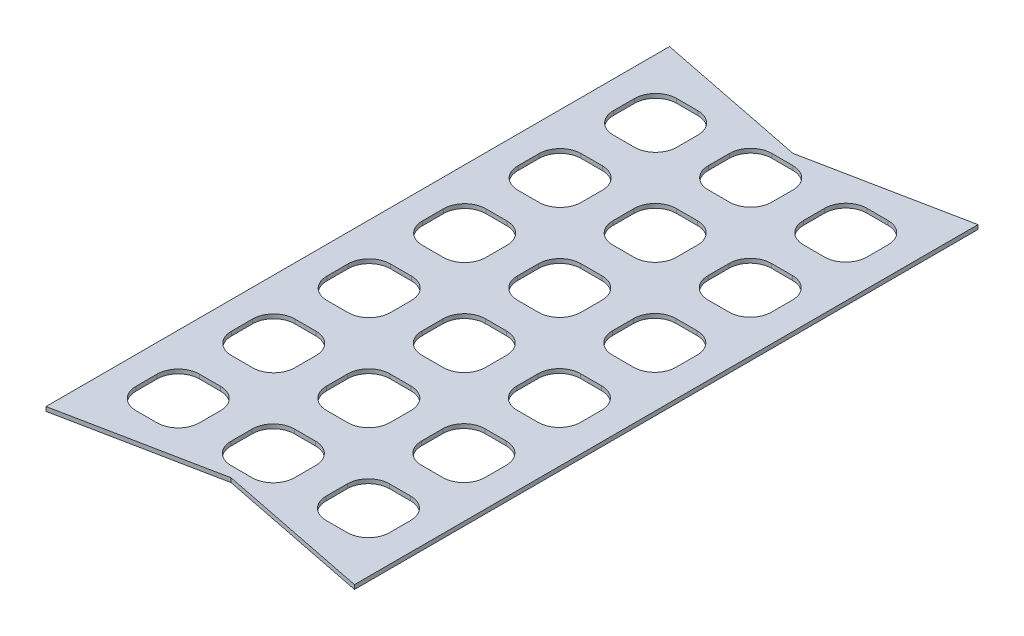
SolidWorks part; units mm, degrees
ref_plane "Front Plane" through (0, 0, 0) normal (0, 0, 1) x (1, 0, 0)
ref_plane "Top Plane" through (0, 0, 0) normal (0, 1, 0) x (1, 0, 0)
ref_plane "Right Plane" through (0, 0, 0) normal (1, 0, 0) x (0, 0, -1)
ref_axis "X" through (-88.99, 0, 0) along (1, 0, 0)
ref_axis "Y" through (0, 55, 0) along (0, -1, 0)
ref_axis "Z" through (0, 0, -88.99) along (0, 0, 1)
sketch "Sketch1" plane through (0, 0, 0) normal (0, 1, 0) x (1, 0, 0)
  line L0 (-75, 150) -> (0, 135) construction
  line L1 (-75, 150) -> (75, 150) construction
  line L2 (-75, 150) -> (-75, -150) construction
  line L3 (-75, -150) -> (75, -150) construction
  line L4 (75, 150) -> (75, -150) construction
  line L5 (-75, 150) -> (75, -150) construction
  line L6 (-75, -150) -> (75, 150) construction
  line L7 (0, 135) -> (75, 150) construction
  line L8 (-75, 0) -> (75, 0) construction
  line L9 (-75, -150) -> (0, -135) construction
  line L10 (0, -135) -> (75, -150) construction
  line L11 (-73, 147.5604) -> (-73, -147.5604)
  line L12 (-73, -147.5604) -> (0, -132.9604)
  line L13 (0, -132.9604) -> (73, -147.5604)
  line L14 (73, 147.5604) -> (73, -147.5604)
  line L15 (0, 132.9604) -> (73, 147.5604)
  line L16 (-73, 147.5604) -> (0, 132.9604)
  point P0 (0, 0)
  point P10 (-75, 150)
  dimension "D1" = 300
  dimension "D2" = 150
  dimension "D3" = 15
  dimension "D4" = 2
extrude "Boss-Extrude1" add sketch "Sketch1" along normal blind 2
sketch "Sketch2" plane through (0, 2, 0) normal (0, 1, 0) x (1, 0, 0)
  line L0 (-73, 147.5604) -> (-73, -147.5604) construction
  line L1 (-50, -127.9604) -> (-40, -127.9604)
  line L2 (-60, -117.9604) -> (-60, -107.9604)
  line L3 (-50, -97.9604) -> (-40, -97.9604)
  line L4 (-30, -117.9604) -> (-30, -107.9604)
  line L5 (-15, -117.9604) -> (-15, -107.9604)
  line L6 (-5, -127.9604) -> (5, -127.9604)
  line L7 (15, -117.9604) -> (15, -107.9604)
  line L8 (-5, -97.9604) -> (5, -97.9604)
  line L9 (30, -117.9604) -> (30, -107.9604)
  line L10 (40, -127.9604) -> (50, -127.9604)
  line L11 (60, -117.9604) -> (60, -107.9604)
  line L12 (40, -97.9604) -> (50, -97.9604)
  line L73 (-60, -72.7762) -> (-60, -62.7762)
  line L74 (-50, -82.7762) -> (-40, -82.7762)
  line L75 (-30, -72.7762) -> (-30, -62.7762)
  line L76 (-50, -52.7762) -> (-40, -52.7762)
  line L77 (-15, -72.7762) -> (-15, -62.7762)
  line L78 (-5, -52.7762) -> (5, -52.7762)
  line L79 (15, -72.7762) -> (15, -62.7762)
  line L80 (-5, -82.7762) -> (5, -82.7762)
  line L81 (30, -72.7762) -> (30, -62.7762)
  line L82 (40, -52.7762) -> (50, -52.7762)
  line L83 (60, -72.7762) -> (60, -62.7762)
  line L84 (40, -82.7762) -> (50, -82.7762)
  line L85 (-60, -27.5921) -> (-60, -17.5921)
  line L86 (-50, -37.5921) -> (-40, -37.5921)
  line L87 (-30, -27.5921) -> (-30, -17.5921)
  line L88 (-50, -7.5921) -> (-40, -7.5921)
  line L89 (-15, -27.5921) -> (-15, -17.5921)
  line L90 (-5, -7.5921) -> (5, -7.5921)
  line L91 (15, -27.5921) -> (15, -17.5921)
  line L92 (-5, -37.5921) -> (5, -37.5921)
  line L93 (30, -27.5921) -> (30, -17.5921)
  line L94 (40, -7.5921) -> (50, -7.5921)
  line L95 (60, -27.5921) -> (60, -17.5921)
  line L96 (40, -37.5921) -> (50, -37.5921)
  line L97 (-60, 17.5921) -> (-60, 27.5921)
  line L98 (-50, 7.5921) -> (-40, 7.5921)
  line L99 (-30, 17.5921) -> (-30, 27.5921)
  line L100 (-50, 37.5921) -> (-40, 37.5921)
  line L101 (-15, 17.5921) -> (-15, 27.5921)
  line L102 (-5, 37.5921) -> (5, 37.5921)
  line L103 (15, 17.5921) -> (15, 27.5921)
  line L104 (-5, 7.5921) -> (5, 7.5921)
  line L105 (30, 17.5921) -> (30, 27.5921)
  line L106 (40, 37.5921) -> (50, 37.5921)
  line L107 (60, 17.5921) -> (60, 27.5921)
  line L108 (40, 7.5921) -> (50, 7.5921)
  line L109 (-60, 62.7762) -> (-60, 72.7762)
  line L110 (-50, 52.7762) -> (-40, 52.7762)
  line L111 (-30, 62.7762) -> (-30, 72.7762)
  line L112 (-50, 82.7762) -> (-40, 82.7762)
  line L113 (-15, 62.7762) -> (-15, 72.7762)
  line L114 (-5, 82.7762) -> (5, 82.7762)
  line L115 (15, 62.7762) -> (15, 72.7762)
  line L116 (-5, 52.7762) -> (5, 52.7762)
  line L117 (30, 62.7762) -> (30, 72.7762)
  line L118 (40, 82.7762) -> (50, 82.7762)
  line L119 (60, 62.7762) -> (60, 72.7762)
  line L120 (40, 52.7762) -> (50, 52.7762)
  line L121 (-60, 107.9604) -> (-60, 117.9604)
  line L122 (-50, 97.9604) -> (-40, 97.9604)
  line L123 (-30, 107.9604) -> (-30, 117.9604)
  line L124 (-50, 127.9604) -> (-40, 127.9604)
  line L125 (-15, 107.9604) -> (-15, 117.9604)
  line L126 (-5, 127.9604) -> (5, 127.9604)
  line L127 (15, 107.9604) -> (15, 117.9604)
  line L128 (-5, 97.9604) -> (5, 97.9604)
  line L129 (30, 107.9604) -> (30, 117.9604)
  line L130 (40, 127.9604) -> (50, 127.9604)
  line L131 (60, 107.9604) -> (60, 117.9604)
  line L132 (40, 97.9604) -> (50, 97.9604)
  arc A0 (-60, -117.9604) -> (-50, -127.9604) centre (-50, -117.9604) ccw
  arc A1 (-40, -127.9604) -> (-30, -117.9604) centre (-40, -117.9604) ccw
  arc A2 (-30, -107.9604) -> (-40, -97.9604) centre (-40, -107.9604) ccw
  arc A3 (-50, -97.9604) -> (-60, -107.9604) centre (-50, -107.9604) ccw
  arc A4 (60, -107.9604) -> (50, -97.9604) centre (50, -107.9604) ccw
  arc A5 (50, -127.9604) -> (60, -117.9604) centre (50, -117.9604) ccw
  arc A6 (40, -127.9604) -> (30, -117.9604) centre (40, -117.9604) cw
  arc A7 (30, -107.9604) -> (40, -97.9604) centre (40, -107.9604) cw
  arc A8 (-15, -107.9604) -> (-5, -97.9604) centre (-5, -107.9604) cw
  arc A9 (-15, -117.9604) -> (-5, -127.9604) centre (-5, -117.9604) ccw
  arc A10 (15, -117.9604) -> (5, -127.9604) centre (5, -117.9604) cw
  arc A11 (15, -107.9604) -> (5, -97.9604) centre (5, -107.9604) ccw
  arc A12 (-50, -52.7762) -> (-60, -62.7762) centre (-50, -62.7762) ccw
  arc A13 (-60, -72.7762) -> (-50, -82.7762) centre (-50, -72.7762) ccw
  arc A14 (-40, -82.7762) -> (-30, -72.7762) centre (-40, -72.7762) ccw
  arc A15 (-30, -62.7762) -> (-40, -52.7762) centre (-40, -62.7762) ccw
  arc A16 (-15, -72.7762) -> (-5, -82.7762) centre (-5, -72.7762) ccw
  arc A17 (-15, -62.7762) -> (-5, -52.7762) centre (-5, -62.7762) cw
  arc A18 (15, -62.7762) -> (5, -52.7762) centre (5, -62.7762) ccw
  arc A19 (15, -72.7762) -> (5, -82.7762) centre (5, -72.7762) cw
  arc A20 (30, -62.7762) -> (40, -52.7762) centre (40, -62.7762) cw
  arc A21 (40, -82.7762) -> (30, -72.7762) centre (40, -72.7762) cw
  arc A22 (60, -62.7762) -> (50, -52.7762) centre (50, -62.7762) ccw
  arc A23 (50, -82.7762) -> (60, -72.7762) centre (50, -72.7762) ccw
  arc A24 (-50, -7.5921) -> (-60, -17.5921) centre (-50, -17.5921) ccw
  arc A25 (-60, -27.5921) -> (-50, -37.5921) centre (-50, -27.5921) ccw
  arc A26 (-40, -37.5921) -> (-30, -27.5921) centre (-40, -27.5921) ccw
  arc A27 (-30, -17.5921) -> (-40, -7.5921) centre (-40, -17.5921) ccw
  arc A28 (-15, -27.5921) -> (-5, -37.5921) centre (-5, -27.5921) ccw
  arc A29 (-15, -17.5921) -> (-5, -7.5921) centre (-5, -17.5921) cw
  arc A30 (15, -17.5921) -> (5, -7.5921) centre (5, -17.5921) ccw
  arc A31 (15, -27.5921) -> (5, -37.5921) centre (5, -27.5921) cw
  arc A32 (30, -17.5921) -> (40, -7.5921) centre (40, -17.5921) cw
  arc A33 (40, -37.5921) -> (30, -27.5921) centre (40, -27.5921) cw
  arc A34 (60, -17.5921) -> (50, -7.5921) centre (50, -17.5921) ccw
  arc A35 (50, -37.5921) -> (60, -27.5921) centre (50, -27.5921) ccw
  arc A36 (-50, 37.5921) -> (-60, 27.5921) centre (-50, 27.5921) ccw
  arc A37 (-60, 17.5921) -> (-50, 7.5921) centre (-50, 17.5921) ccw
  arc A38 (-40, 7.5921) -> (-30, 17.5921) centre (-40, 17.5921) ccw
  arc A39 (-30, 27.5921) -> (-40, 37.5921) centre (-40, 27.5921) ccw
  arc A40 (-15, 17.5921) -> (-5, 7.5921) centre (-5, 17.5921) ccw
  arc A41 (-15, 27.5921) -> (-5, 37.5921) centre (-5, 27.5921) cw
  arc A42 (15, 27.5921) -> (5, 37.5921) centre (5, 27.5921) ccw
  arc A43 (15, 17.5921) -> (5, 7.5921) centre (5, 17.5921) cw
  arc A44 (30, 27.5921) -> (40, 37.5921) centre (40, 27.5921) cw
  arc A45 (40, 7.5921) -> (30, 17.5921) centre (40, 17.5921) cw
  arc A46 (60, 27.5921) -> (50, 37.5921) centre (50, 27.5921) ccw
  arc A47 (50, 7.5921) -> (60, 17.5921) centre (50, 17.5921) ccw
  arc A48 (-50, 82.7762) -> (-60, 72.7762) centre (-50, 72.7762) ccw
  arc A49 (-60, 62.7762) -> (-50, 52.7762) centre (-50, 62.7762) ccw
  arc A50 (-40, 52.7762) -> (-30, 62.7762) centre (-40, 62.7762) ccw
  arc A51 (-30, 72.7762) -> (-40, 82.7762) centre (-40, 72.7762) ccw
  arc A52 (-15, 62.7762) -> (-5, 52.7762) centre (-5, 62.7762) ccw
  arc A53 (-15, 72.7762) -> (-5, 82.7762) centre (-5, 72.7762) cw
  arc A54 (15, 72.7762) -> (5, 82.7762) centre (5, 72.7762) ccw
  arc A55 (15, 62.7762) -> (5, 52.7762) centre (5, 62.7762) cw
  arc A56 (30, 72.7762) -> (40, 82.7762) centre (40, 72.7762) cw
  arc A57 (40, 52.7762) -> (30, 62.7762) centre (40, 62.7762) cw
  arc A58 (60, 72.7762) -> (50, 82.7762) centre (50, 72.7762) ccw
  arc A59 (50, 52.7762) -> (60, 62.7762) centre (50, 62.7762) ccw
  arc A60 (-50, 127.9604) -> (-60, 117.9604) centre (-50, 117.9604) ccw
  arc A61 (-60, 107.9604) -> (-50, 97.9604) centre (-50, 107.9604) ccw
  arc A62 (-40, 97.9604) -> (-30, 107.9604) centre (-40, 107.9604) ccw
  arc A63 (-30, 117.9604) -> (-40, 127.9604) centre (-40, 117.9604) ccw
  arc A64 (-15, 107.9604) -> (-5, 97.9604) centre (-5, 107.9604) ccw
  arc A65 (-15, 117.9604) -> (-5, 127.9604) centre (-5, 117.9604) cw
  arc A66 (15, 117.9604) -> (5, 127.9604) centre (5, 117.9604) ccw
  arc A67 (15, 107.9604) -> (5, 97.9604) centre (5, 107.9604) cw
  arc A68 (30, 117.9604) -> (40, 127.9604) centre (40, 117.9604) cw
  arc A69 (40, 97.9604) -> (30, 107.9604) centre (40, 107.9604) cw
  arc A70 (60, 117.9604) -> (50, 127.9604) centre (50, 117.9604) ccw
  arc A71 (50, 97.9604) -> (60, 107.9604) centre (50, 107.9604) ccw
  point P81 (-30, -127.9604)
  point P84 (-30, -97.9604)
  point P87 (-60, -97.9604)
  dimension "D9" = 10
  dimension "D7" = 10
  dimension "D1" = 30
  dimension "D2" = 30
  dimension "D3" = 13
  dimension "D4" = 5
  dimension "D6" = 15
  dimension "D8" = 6
  dimension "D10" = 5
  dimension "D5" = 3
extrude "Cut-Extrude1" cut sketch "Sketch2" against normal through all
